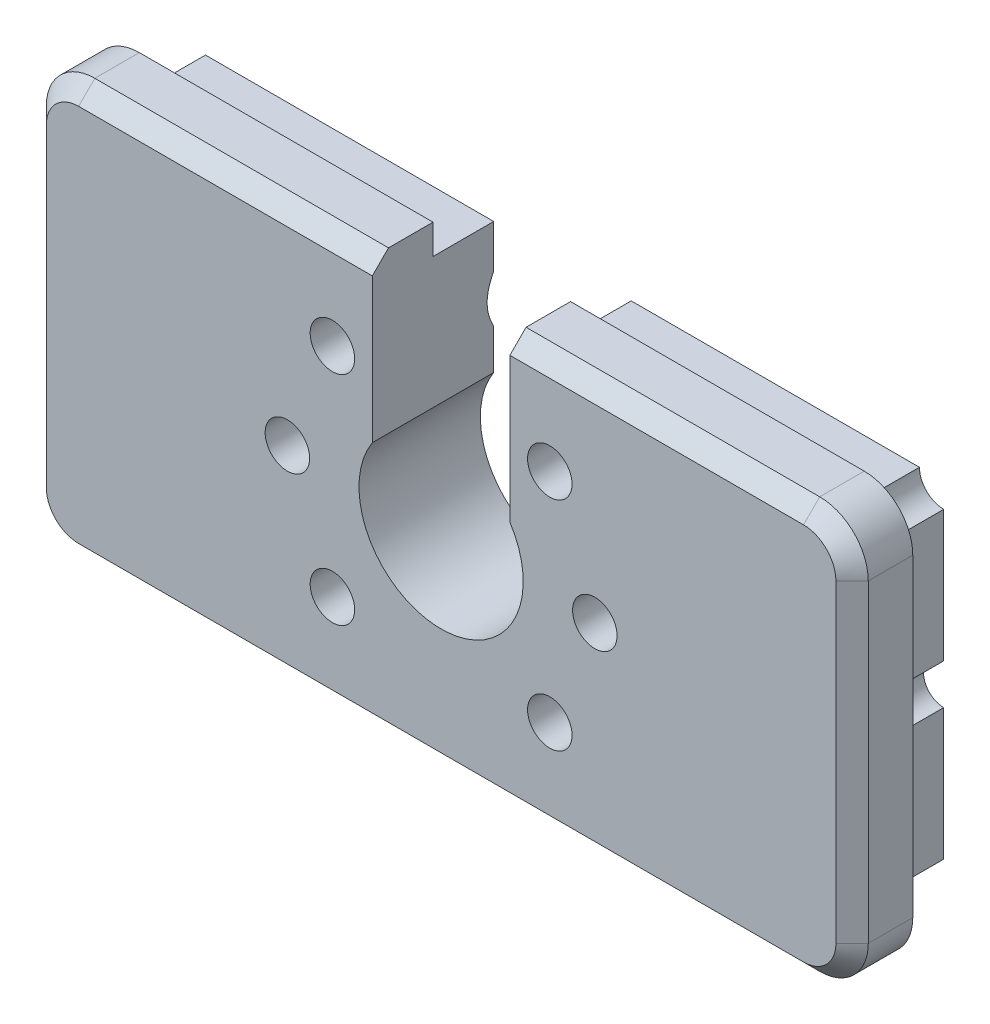
SolidWorks part; units mm, degrees
material "PET"
ref_plane "Front Plane" through (0, 0, 0) normal (0, 0, 1) x (1, 0, 0)
ref_plane "Top Plane" through (0, 0, 0) normal (0, 1, 0) x (1, 0, 0)
ref_plane "Right Plane" through (0, 0, 0) normal (1, 0, 0) x (0, 0, -1)
sketch "Sketch1" plane through (0, 0, 0) normal (0, 0, 1) x (1, 0, 0)
  line L1 (50.8, -25.4) -> (-50.8, -25.4)
  line L2 (50.8, -25.4) -> (50.8, 25.4)
  line L3 (50.8, 25.4) -> (-50.8, 25.4)
  line L4 (-50.8, -25.4) -> (-50.8, 25.4)
  line L5 (50.8, -25.4) -> (-50.8, 25.4) construction
  line L6 (50.8, 25.4) -> (-50.8, -25.4) construction
  point P0 (0, 0)
  dimension "D1" = 50.8
  dimension "D2" = 101.6
extrude "Boss-Extrude1" add sketch "Sketch1" against normal blind 7.5
sketch "Sketch2" plane through (0, 0, -7.5) normal (0, 0, -1) x (-1, 0, 0)
  line L8 (47.125, -21.725) -> (47.125, 21.725)
  line L9 (47.125, 21.725) -> (-47.125, 21.725)
  line L10 (-47.125, 21.725) -> (-47.125, -21.725)
  line L11 (-47.125, -21.725) -> (47.125, -21.725)
  line L12 (47.125, -21.725) -> (47.125, 21.725)
  line L13 (47.125, 21.725) -> (-47.125, 21.725)
  line L14 (-47.125, 21.725) -> (-47.125, -21.725)
  line L15 (-47.125, -21.725) -> (47.125, -21.725)
  dimension "D1" = 3.675
extrude "Boss-Extrude2" add sketch "Sketch2" along normal blind 7.5
sketch "Sketch3" plane through (0, 0, 0) normal (0, 0, 1) x (1, 0, 0)
  line L0 (0, 0) -> (0, 51.1675) construction
  line L1 (50.8, 25.4) -> (-50.8, 25.4) construction
  line L2 (8.5, 5.5473) -> (-8.5, 5.5473) construction
  line L3 (8.5, 5.5473) -> (8.5, 25.4)
  line L4 (8.5, 25.4) -> (-8.5, 25.4)
  line L5 (-8.5, 5.5473) -> (-8.5, 25.4)
  line L6 (8.5, 5.5473) -> (-8.5, 25.4) construction
  line L7 (8.5, 25.4) -> (-8.5, 5.5473) construction
  line L8 (0, 0) -> (-19, 0) construction
  arc A0 (-8.5, 5.5473) -> (8.5, 5.5473) centre (0, 0) ccw
  circle A1 centre (-19, 0) radius 2.75
  circle A2 centre (-13.435, 13.435) radius 2.75
  circle A3 centre (0, 19) radius 2.75 construction
  circle A4 centre (13.435, 13.435) radius 2.75
  circle A5 centre (19, 0) radius 2.75
  circle A6 centre (13.435, -13.435) radius 2.75
  circle A7 centre (0, -19) radius 2.75 construction
  circle A8 centre (-13.435, -13.435) radius 2.75
  point P3 (0, 15.4736)
  point P28 (0, 0)
  dimension "D4" = 5.5
  dimension "D2" = 17
  dimension "D3" = 19
  dimension "D5" = 8
extrude "Cut-Extrude1" cut sketch "Sketch3" against normal through all
fillet "Fillet1" radius 6 4 edges at (50.8, -25.4, -3.75) (-50.8, -25.4, -3.75) (-50.8, 25.4, -3.75) (50.8, 25.4, -3.75)
sketch "Sketch4" plane through (0, 0, -15) normal (0, 0, -1) x (-1, 0, 0)
  line L0 (-47.125, 21.725) -> (-47.125, -21.725) construction
  line L3 (-8.5, 21.725) -> (-47.125, 21.725) construction
  line L5 (-47.125, -21.725) -> (0, -21.725) construction
  line L6 (0, 0) -> (0, -21.725) construction
  line L7 (-47.125, 21.725) -> (-47.125, -21.725) construction
  circle A0 centre (-47.125, 21.725) radius 3
  circle A1 centre (-47.125, -21.725) radius 3
  circle A2 centre (-47.125, 0) radius 2.5
  circle A3 centre (0, -21.725) radius 2.5
  circle A4 centre (47.125, -21.725) radius 3
  circle A5 centre (47.125, 0) radius 2.5
  circle A6 centre (47.125, 21.725) radius 3
  arc A7 (-44.8, 25.4) -> (-50.8, 19.4) centre (-44.8, 19.4) ccw construction
  arc A8 (-44.8, 25.4) -> (-50.8, 19.4) centre (-44.8, 19.4) ccw construction
  dimension "D4" = 5
  dimension "D5" = 6
  dimension "D1" = 6
extrude "Cut-Extrude2" cut sketch "Sketch4" against normal up to surface (7.5 mm away) up to face at (0, 5.8906, -7.5)
chamfer "Chamfer1" distance 2 angle 45 9 edges at (-26.65, 25.4, 0) (-49.0426, 23.6426, 0) (-50.8, 0, 0) (-49.0426, -23.6426, 0) (0, -25.4, 0) (49.0426, -23.6426, 0) (50.8, 0, 0) (49.0426, 23.6426, 0) (26.65, 25.4, 0)
chamfer "Chamfer2" distance 3 angle 45 6 edges at (16.185, -13.435, -15) (-16.25, 0, -15) (-10.685, -13.435, -15) (21.75, 0, -15) (16.185, 13.435, -15) (-10.685, 13.435, -15)
equation "\"hole_radius\"= 10.15mm"
equation "\"D1@Sketch3\"=\"hole_radius\"*2"
equation "\"M5_tap\"=4.2mm       ' Below you can do mesurements as follows: cm, mm, ft, in, m, "
equation "\"M5_clearence\"=5.5mm"
equation "\"M6_tap\"=5mm"
equation "\"M6_clearence\"=6.6mm"
equation "\"work_area_width\"=1100mm"
equation "\"work_area_depth\"=900mm"
equation "\"steel_base_width\"=3in "
equation "\"steel_base_height\"=2in"
equation "\"steel_base_wall_thickness\"=0.125in"
equation "\"steel_base_radius\"=6mm"
equation "\"steel_sides_width\"=3in     'this tube is rotated so flip width/height"
equation "\"steel_sides_height\"=2in    'this tube is rotated so flip width/height"
equation "\"steel_sides_wall_thickness\"=0.125in"
equation "\"steel_sides_radius\"=6mm"
equation "\"steel_gantry_width\"=4in    'this tube is rotated so flip width/height"
equation "\"steel_gantry_height\"=3in    'this tube is rotated so flip width/height"
equation "\"steel_gantry_wall_thickness\"=0.125in"
equation "\"steel_gantry_radius\"=6mm"
equation "\"steel_rollers_width\"=3in"
equation "\"steel_rollers_height\"=2in    'keep as low as possible as this increases how big plastic parts are"
equation "\"steel_rollers_wall_thickness\"=0.125in"
equation "\"steel_rollers_radius\"=6mm"
equation "\"steel_zbox_width\"=4in     'if the gantry height (rotated) is too thick, a wider zbox is necessary"
equation "\"steel_zbox_height\"=2in     'hole patteren changes as the zbox and gantry height (rotated) changes."
equation "\"steel_zbox_wall_thickness\"=0.125in"
equation "\"steel_zbox_radius\"=6mm"
equation "\"D2@Sketch1\"=\"steel_zbox_width\""
equation "\"D1@Sketch1\"=\"steel_zbox_height\""
equation "\"D1@Sketch2\"=\"steel_zbox_wall_thickness\"+ 0.5mm"
equation "\"D1@Fillet1\"=\"steel_zbox_radius\""
equation "\"D5@Sketch4\"=\"D1@Sketch4\""
